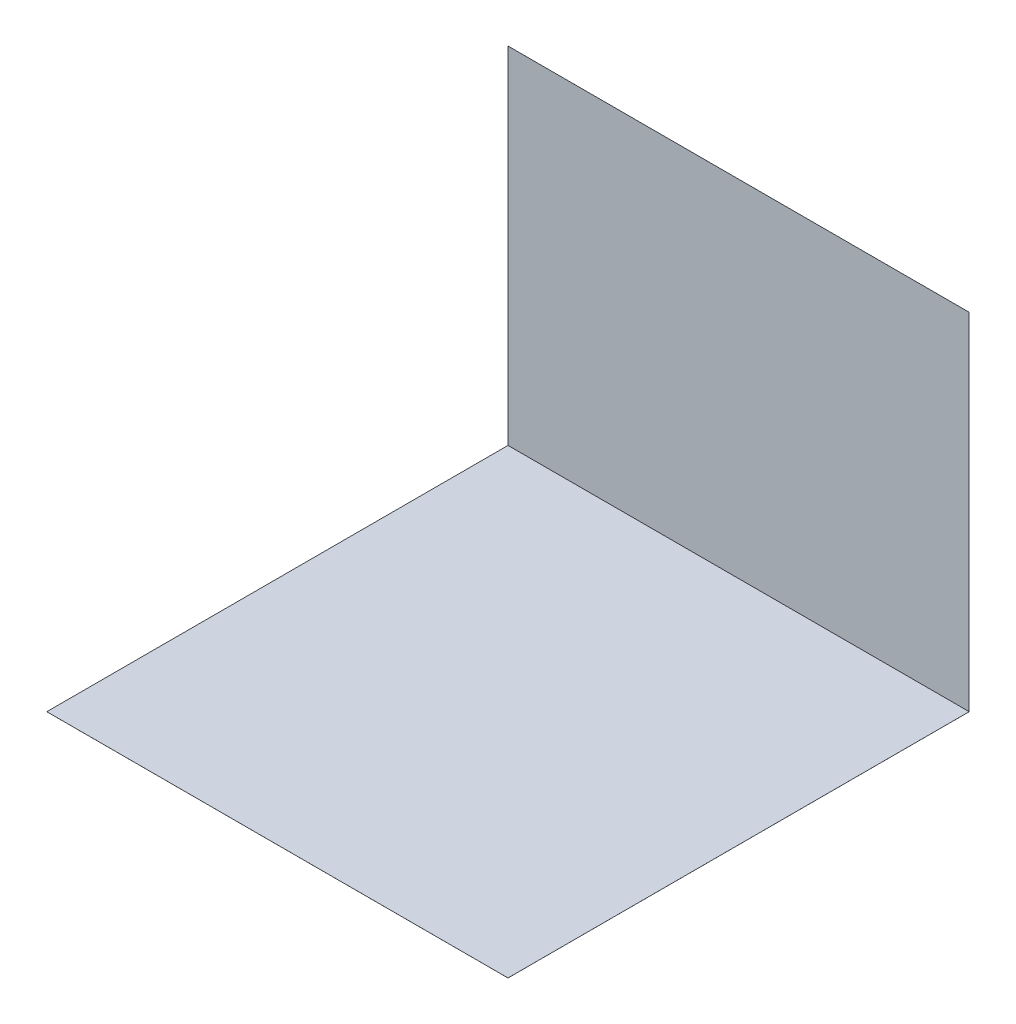
SolidWorks part; units mm, degrees
other "Floor"
ref_plane "Front Plane" through (0, 0, 0) normal (0, 0, 1) x (1, 0, 0)
ref_plane "Top Plane" through (0, 0, 0) normal (0, 1, 0) x (1, 0, 0)
ref_plane "Right Plane" through (0, 0, 0) normal (1, 0, 0) x (0, 0, -1)
sketch "Sketch2" plane through (0, 0, 0) normal (0, 1, 0) x (1, 0, 0)
  line L1 (-83.0204, 20.3435) -> (3916.9796, 20.3435)
  line L2 (-83.0204, 20.3435) -> (-83.0204, -3979.6565)
  line L3 (-83.0204, -3979.6565) -> (3916.9796, -3979.6565)
  line L4 (3916.9796, 20.3435) -> (3916.9796, -3979.6565)
  dimension "Width_Floor" = 4000
  dimension "Length_Floor" = 4000
extrude "Floor" add sketch "Sketch2" along normal blind 0.254
sketch "Sketch4" plane through (0, 0.254, 0) normal (0, 1, 0) x (1, 0, 0)
  line L0 (3916.9796, 20.3435) -> (-83.0204, 20.3435) construction
  line L1 (3916.9796, 20.3435) -> (-83.0204, 20.3435)
  dimension "wallBase" = 4000
extrude "Wall1" add sketch "Sketch4" along normal blind 3000 separate body thin thin type one direction wall 0.0254
sketch "Sketch5" [suppressed] plane through (0, 0, -20.3689) normal (0, 0, -1) x (-1, 0, 0)
  line L0 (-4916.9796, 0.254) -> (83.0204, 0.254) construction
  line L1 (-2.7195, 11.5038) -> (-2.6941, 11.5038)
  line L2 (-2.7195, 11.5038) -> (-2.7195, 11.4784)
  line L3 (-2.7195, 11.4784) -> (-2.6941, 11.4784)
  line L4 (-2.6941, 11.5038) -> (-2.6941, 11.4784)
  line L5 (83.0204, 3000.254) -> (83.0204, 0.254) construction
  dimension "Window1Display" = 0
  dimension "Window1Length" = 0
  dimension "Window1BottomOffset" = 0
  dimension "Window1RightOffset" = 0
extrude "WindowSlot1" [suppressed] cut sketch "Sketch5" against normal through all
sketch "Sketch7" [suppressed] plane through (0, 0, -20.3689) normal (0, 0, -1) x (-1, 0, 0)
  line L0 (-4916.9796, 0.254) -> (83.0204, 0.254) construction
  line L1 (33.338, 5.5809) -> (33.3634, 5.5809)
  line L2 (33.338, 5.5809) -> (33.338, 5.5555)
  line L3 (33.338, 5.5555) -> (33.3634, 5.5555)
  line L4 (33.3634, 5.5809) -> (33.3634, 5.5555)
  line L5 (83.0204, 3000.254) -> (83.0204, 0.254) construction
  dimension "Window2Display" = 0
  dimension "Window2Length" = 0
  dimension "Window2BottomOffset" = 0
  dimension "Window2RightOffset" = 0
extrude "WindowSlot2" [suppressed] cut sketch "Sketch7" against normal through all
sketch "Sketch8" [suppressed] plane through (0, 0, -20.3689) normal (0, 0, -1) x (-1, 0, 0)
  line L0 (-4916.9796, 0.254) -> (83.0204, 0.254) construction
  line L1 (69.0838, 8.4904) -> (69.1092, 8.4904)
  line L2 (69.0838, 8.4904) -> (69.0838, 8.465)
  line L3 (69.0838, 8.465) -> (69.1092, 8.465)
  line L4 (69.1092, 8.4904) -> (69.1092, 8.465)
  line L5 (83.0204, 3000.254) -> (83.0204, 0.254) construction
  dimension "Window3Display" = 0
  dimension "Window3Length" = 0
  dimension "Window3BottomOffset" = 0
  dimension "Window3RightOffset" = 0
extrude "WindowSlot3" [suppressed] cut sketch "Sketch8" against normal through all
sketch "Sketch9" [suppressed] plane through (0, 0, -20.3689) normal (0, 0, -1) x (-1, 0, 0)
  line L0 (-4916.9796, 0.254) -> (83.0204, 0.254) construction
  line L1 (-2.5117, 3.2948) -> (-2.4863, 3.2948)
  line L2 (-2.5117, 3.2948) -> (-2.5117, 3.2694)
  line L3 (-2.5117, 3.2694) -> (-2.4863, 3.2694)
  line L4 (-2.4863, 3.2948) -> (-2.4863, 3.2694)
  line L5 (83.0204, 3000.254) -> (83.0204, 0.254) construction
  dimension "Door1Display" = 500
  dimension "Door1length" = 0
  dimension "Door1BottomOffset" = 0
  dimension "Door1RightOffset" = 1000
extrude "Door1" [suppressed] cut sketch "Sketch9" against normal through all
sketch "Sketch10" [suppressed] plane through (0, 0, -20.3689) normal (0, 0, -1) x (-1, 0, 0)
  line L0 (-4916.9796, 0.254) -> (83.0204, 0.254) construction
  line L1 (25.025, 5.0613) -> (25.0504, 5.0613)
  line L2 (25.025, 5.0613) -> (25.025, 5.0359)
  line L3 (25.025, 5.0359) -> (25.0504, 5.0359)
  line L4 (25.0504, 5.0613) -> (25.0504, 5.0359)
  line L5 (83.0204, 3000.254) -> (83.0204, 0.254) construction
  dimension "D1" = 0
  dimension "Door2Display" = 0
  dimension "Door2BottomOffset" = 0
  dimension "Door2RightOffset" = 0
extrude "Door2" [suppressed] cut sketch "Sketch10" against normal through all
